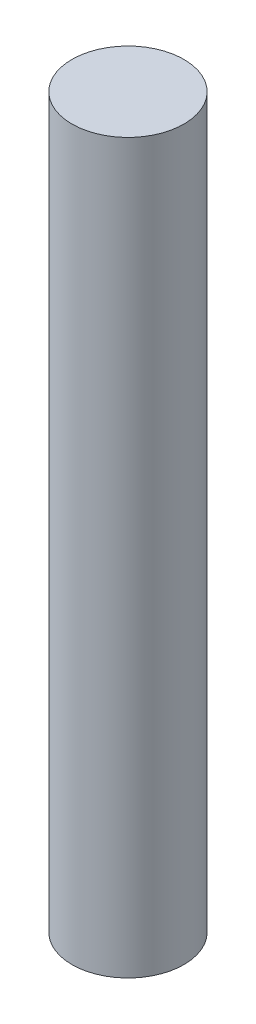
SolidWorks part; units mm, degrees
ref_plane "前视基准面" through (0, 0, 0) normal (0, 0, 1) x (1, 0, 0)
ref_plane "上视基准面" through (0, 0, 0) normal (0, 1, 0) x (1, 0, 0)
ref_plane "右视基准面" through (0, 0, 0) normal (1, 0, 0) x (0, 0, -1)
sketch "草图1" plane through (0, 0, 0) normal (0, 1, 0) x (1, 0, 0)
  circle A0 centre (0, 0) radius 5
  dimension "D1" = 10
extrude "凸台-拉伸1" add sketch "草图1" along normal blind 65
hole_wizard "M4 螺纹孔1" positions "草图4" profile "草图5" tap size "M4" standard "GB"
sketch "草图4" plane through (0, 0, 0) normal (0, -1, 0) x (-1, 0, 0)
  point P0 (0, 0)
sketch "草图5" plane through (0, 0, 0) normal (1, 0, 0) x (0, 0, -1)
  line L0 (0, 0) -> (0, 15.9914)
  line L1 (0, 15.9914) -> (1.65, 15)
  line L2 (1.65, 15) -> (1.65, 0)
  line L5 (1.65, 0) -> (0, 0)
  line L10 (0, 15.9914) -> (-1.65, 15) construction
  line L11 (0, -6.35) -> (0, 107.95) construction
  dimension "螺纹孔钻头直径" = 3.3
  dimension "螺纹孔钻头深度" = 15
  dimension "导头角度" = 118
cosmetic thread "孔螺蚊线1" parameters "D1"=8, "D2"=4
